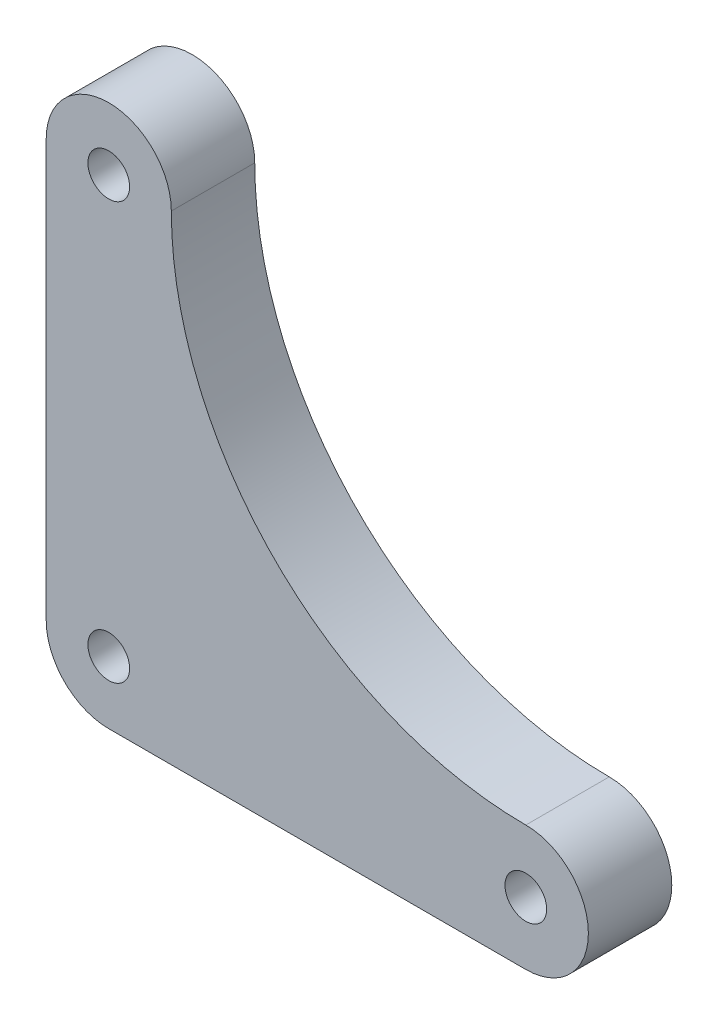
SolidWorks part; units mm, degrees
ref_plane "Front Plane" through (0, 0, 0) normal (0, 0, 1) x (1, 0, 0)
ref_plane "Top Plane" through (0, 0, 0) normal (0, 1, 0) x (1, 0, 0)
ref_plane "Right Plane" through (0, 0, 0) normal (1, 0, 0) x (0, 0, -1)
sketch "Sketch1" plane through (0, 0, 0) normal (0, 0, 1) x (1, 0, 0)
  line L0 (-7.5, 0) -> (-7.5, 50)
  line L1 (0, -7.5) -> (50, -7.5)
  circle A0 centre (0, 0) radius 2.5
  circle A1 centre (50, 0) radius 2.5
  circle A2 centre (0, 50) radius 2.5
  arc A3 (-7.5, 50) -> (7.5, 50) centre (0, 50) cw
  arc A4 (50, 7.5) -> (50, -7.5) centre (50, 0) cw
  arc A5 (-7.5, 0) -> (0, -7.5) centre (0, 0) ccw
  arc A6 (7.5, 50) -> (50, 7.5) centre (50, 50) ccw
  point P14 (0, 0)
  point P15 (0, 0)
  point P16 (0, 0)
  point P17 (31.5137, 25.092)
  point P18 (35.2041, 32.9083)
  point P19 (0, 0)
  point P20 (0, 0)
  dimension "D1" = 5
  dimension "D4" = 5
  dimension "D5" = 5
  dimension "D6" = 5
  dimension "D2" = 50
  dimension "D3" = 50
extrude "Boss-Extrude1" add sketch "Sketch1" along normal blind 10
